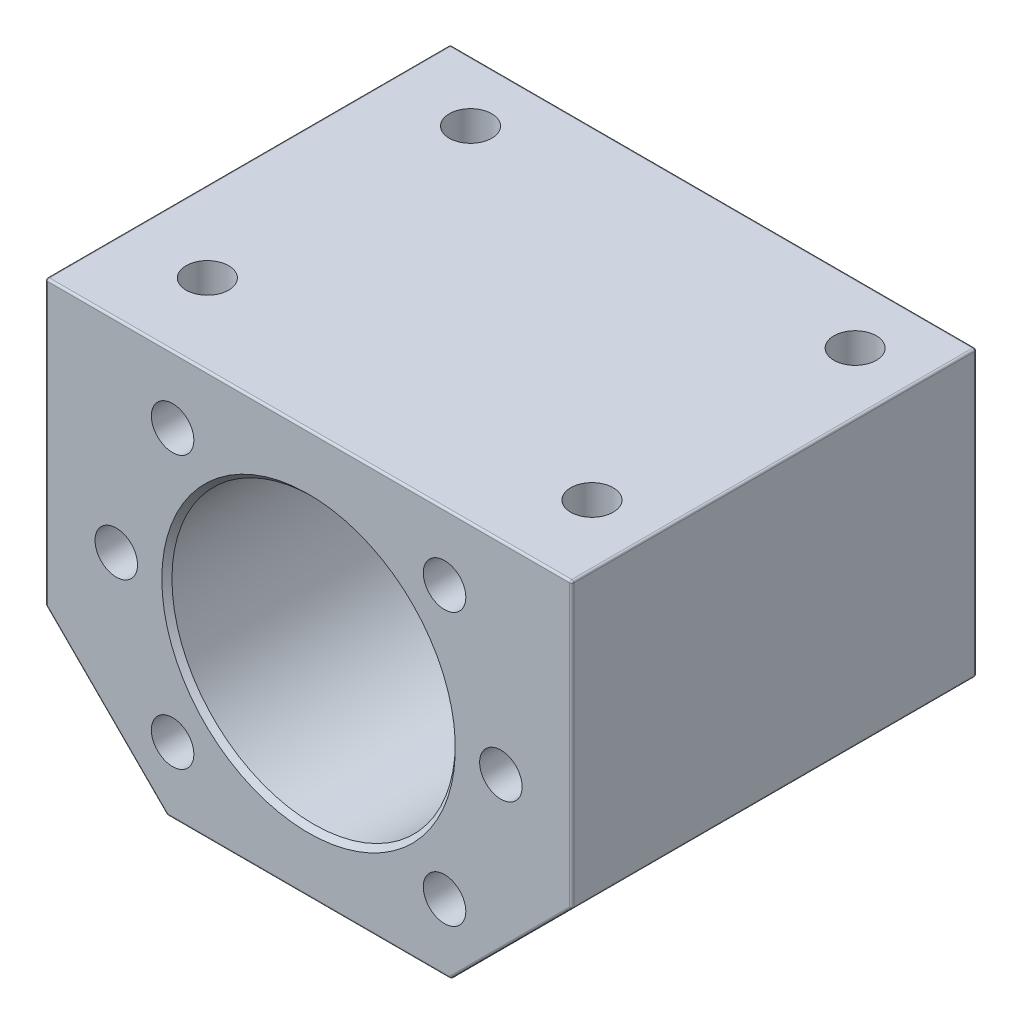
SolidWorks part; units mm, degrees
ref_plane "Ebene vorne" through (0, 0, 0) normal (0, 0, 1) x (1, 0, 0)
ref_plane "Ebene oben" through (0, 0, 0) normal (0, 1, 0) x (1, 0, 0)
ref_plane "Ebene rechts" through (0, 0, 0) normal (1, 0, 0) x (0, 0, -1)
sketch "Skizze1" plane through (0, 0, 0) normal (0, 0, 1) x (1, 0, 0)
  line L0 (12, 0) -> (0, 12)
  line L1 (0, 12) -> (0, 40)
  line L2 (0, 40) -> (52, 40)
  line L3 (52, 40) -> (52, 12)
  line L4 (52, 12) -> (40, 0)
  line L5 (40, 0) -> (12, 0)
  dimension "D1" = 52
  dimension "D2" = 40
  dimension "D3" = 12
  dimension "D4" = 12
  dimension "D5" = 12
  dimension "D6" = 0
extrude "Aufsatz-Linear austragen1" add sketch "Skizze1" along normal blind 40
sketch "Skizze2" plane through (0, 0, 40) normal (0, 0, 1) x (1, 0, 0)
  circle A0 centre (26, 20) radius 14
extrude "Schnitt-Linear austragen1" cut sketch "Skizze2" against normal blind 40
sketch "Skizze16" plane through (0, 0, 40) normal (0, 0, 1) x (1, 0, 0)
  circle A0 centre (26, 20) radius 19
hole_wizard "M5 Gewindebohrung2" positions "Skizze18" profile "Skizze17" tap size "M5" standard "DIN"
sketch "Skizze18" plane through (0, 0, 40) normal (0, 0, 1) x (1, 0, 0)
  circle A0 centre (26, 20) radius 19 construction
  point P0 (7, 20)
  point P4 (45, 20)
  point P6 (39.435, 33.435)
  point P11 (12.565, 33.435)
  point P13 (12.565, 6.565)
  point P15 (39.435, 6.565)
  dimension "D1" = 45
sketch "Skizze17" plane through (7, 20, 40) normal (1, 0, 0) x (0, -1, 0)
  line L0 (0, 0) -> (0, 15.2618)
  line L1 (0, 15.2618) -> (2.1, 14)
  line L2 (2.1, 14) -> (2.1, 0)
  line L5 (2.1, 0) -> (0, 0)
  line L10 (0, 15.2618) -> (-2.1, 14) construction
  line L11 (0, -6.35) -> (0, 107.95) construction
  dimension "Bohrerdurchmesser" = 4.2
  dimension "Bohrungstiefe" = 14
  dimension "Spitzenwinkel" = 118
cosmetic thread "Bohrungsgewinde7" parameters "D1"=10, "D2"=5
cosmetic thread "Bohrungsgewinde8" parameters "D1"=10, "D2"=5
cosmetic thread "Bohrungsgewinde9" parameters "D1"=10, "D2"=5
cosmetic thread "Bohrungsgewinde10" parameters "D1"=10, "D2"=5
cosmetic thread "Bohrungsgewinde11" parameters "D1"=10, "D2"=5
cosmetic thread "Bohrungsgewinde12" parameters "D1"=10, "D2"=5
hole_wizard "M5 Gewindebohrung3" positions "Skizze20" profile "Skizze19" tap size "M5" standard "DIN"
sketch "Skizze20" plane through (0, 40, 0) normal (0, 1, 0) x (1, 0, 0)
  point P0 (8, -6)
  point P1 (8, -32)
  point P2 (46, -6)
  point P3 (46, -32)
sketch "Skizze19" plane through (8, 40, 6) normal (1, 0, 0) x (0, 0, 1)
  line L0 (0, 0) -> (0, 15.2618)
  line L1 (0, 15.2618) -> (2.1, 14)
  line L2 (2.1, 14) -> (2.1, 0)
  line L5 (2.1, 0) -> (0, 0)
  line L10 (0, 15.2618) -> (-2.1, 14) construction
  line L11 (0, -6.35) -> (0, 107.95) construction
  dimension "Bohrerdurchmesser" = 4.2
  dimension "Bohrungstiefe" = 14
  dimension "Spitzenwinkel" = 118
cosmetic thread "Bohrungsgewinde13" parameters "D1"=10, "D2"=5
cosmetic thread "Bohrungsgewinde14" parameters "D1"=10, "D2"=5
cosmetic thread "Bohrungsgewinde15" parameters "D1"=10, "D2"=5
cosmetic thread "Bohrungsgewinde16" parameters "D1"=10, "D2"=5
chamfer "Fase1" distance 0.5 angle 45 1 edges at (40, 20, 40)
chamfer "Fase2" distance 0.5 angle 45 1 edges at (40, 20, 0)
fillet "Verrundung1" radius 0.2 1 edges at (26, 40, 40)
fillet "Verrundung2" radius 0.2 3 edges at (52, 40, 19.9) (52, 39.9414, 39.9414) (52, 25.9, 40)
fillet "Verrundung3" radius 0.2 3 edges at (45.9, 5.9, 40) (51.9414, 11.9414, 39.9414) (52, 12, 19.9)
fillet "Verrundung4" radius 0.2 3 edges at (25.8586, 0, 40) (39.9172, 0, 39.9414) (40, 0, 19.9)
fillet "Verrundung5" radius 0.2 3 edges at (12, 0, 19.9) (11.9414, 0.0586, 39.9414) (5.9, 6.1, 40)
fillet "Verrundung6" radius 0.2 5 edges at (0, 40, 19.9) (0, 39.9414, 39.9414) (0, 26.0414, 40) (0, 12.0828, 39.9414) (0, 12, 19.9)
fillet "Verrundung7" radius 0.2 12 edges at (0.0152, 12.0063, 0) (0, 25.9414, 0) (0.0586, 39.9414, 0) (26, 40, 0) (51.9414, 39.9414, 0) (52, 25.9414, 0) (51.9848, 12.0063, 0) (46, 6, 0) (39.9937, 0.0152, 0) (26, 0, 0) (12.0063, 0.0152, 0) (6, 6, 0)
